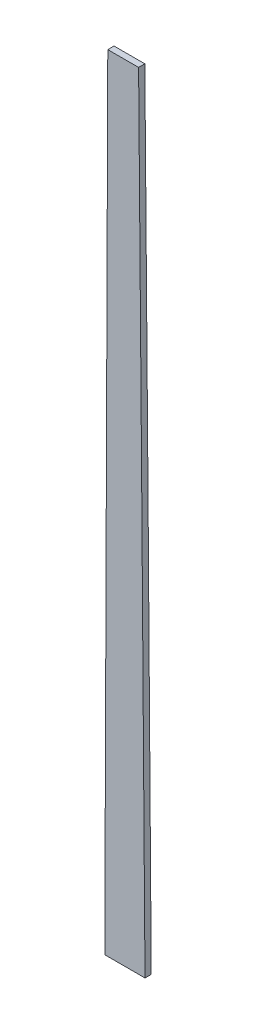
SolidWorks part; units mm, degrees
ref_plane "XY" through (0, 0, 0) normal (0, 0, 1) x (1, 0, 0)
ref_plane "XZ" through (0, 0, 0) normal (0, 1, 0) x (1, 0, 0)
ref_plane "YZ" through (0, 0, 0) normal (1, 0, 0) x (0, 0, -1)
ref_axis "X" through (-88.99, 0, 0) along (1, 0, 0)
ref_axis "Y" through (0, -55, 0) along (0, 1, 0)
ref_axis "Z" through (0, 0, 55) along (0, 0, -1)
sketch "Sketch1" plane through (0, 0, 0) normal (0, 0, 1) x (1, 0, 0)
  spline B0 degree 3 poles (-5.3354, 399.996) (-5.6422, 333.3302) (-5.9156, 266.6643) (-6.4219, 133.3322) (-6.6552, 66.6661) (-6.8747, 0) knots 0 0 0 0 0.5 0.5 1 1 1 1
  spline B1 degree 3 poles (13.6213, 0) (12.6374, 133.3328) (11.5686, 266.665) (10.3597, 399.996) knots 0 0 0 0 1 1 1 1
sketch_block_instance "Block-RearSpar-1"
sketch_block "Block-RearSpar"
sketch "Sketch2" plane through (0, 0, 0) normal (0, 0, 1) x (1, 0, 0)
  line L0 (-6.8747, 0) -> (13.6213, 0)
  line L1 (-5.3354, 399.996) -> (10.3597, 399.996)
  spline S0 degree 3 poles (28.9131, -1999.9394) (12.2471, -533.4463) (18.7098, 933.3561) (-25.1799, 2399.6255) knots -4.999952 -4.999952 -4.999952 -4.999952 5.999593 5.999593 5.999593 5.999593 only from (13.6213, 0) to (10.3597, 399.996) construction
  spline S1 degree 3 poles (27.0972, 2399.6704) (1.8438, 1666.5213) (-3.3839, 933.2643) (-8.9539, -533.3266) (-9.3284, -1266.6606) (-15.4692, -1999.9632) knots -4.999549 -4.999549 -4.999549 -4.999549 0.5 0.5 5.99999 5.99999 5.99999 5.99999 only from (-5.3354, 399.996) to (-6.8747, 0) construction
  spline S2 degree 3 poles (13.6213, 0) (12.6374, 133.3328) (11.5686, 266.665) (10.3597, 399.996) knots 0 0 0 0 1 1 1 1
  spline S3 degree 3 poles (-5.3354, 399.996) (-5.6422, 333.3302) (-5.9156, 266.6643) (-6.4219, 133.3322) (-6.6552, 66.6661) (-6.8747, 0) knots 0 0 0 0 0.5 0.5 1 1 1 1
extrude "Boss-Extrude1" add sketch "Sketch2" along normal blind 3.175
